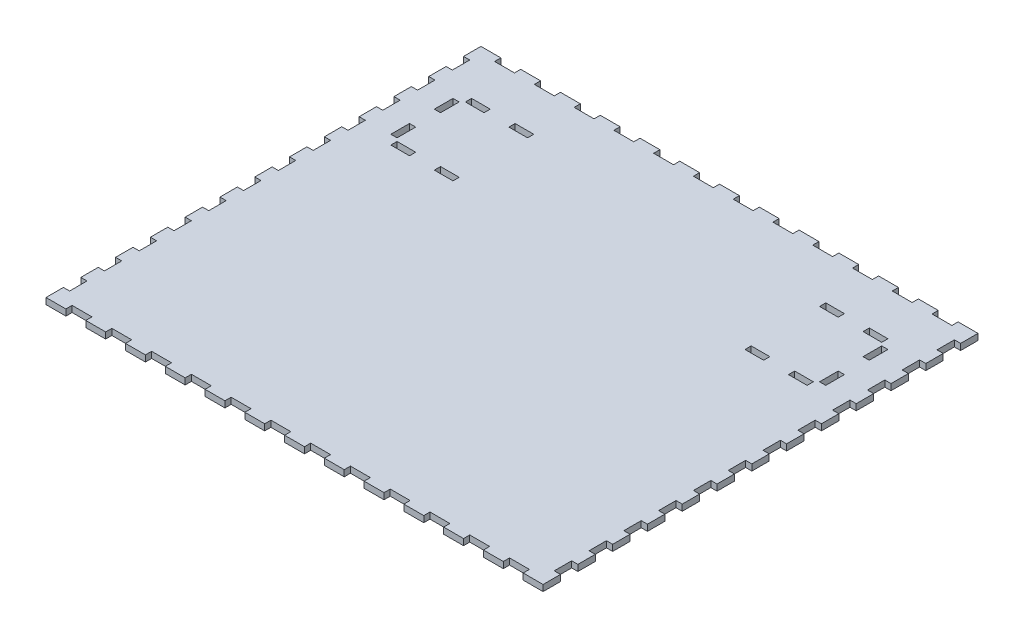
SolidWorks part; units mm, degrees
ref_plane "Plan de face" through (0, 0, 0) normal (0, 0, 1) x (1, 0, 0)
ref_plane "Plan de dessus" through (0, 0, 0) normal (0, 1, 0) x (1, 0, 0)
ref_plane "Plan de droite" through (0, 0, 0) normal (1, 0, 0) x (0, 0, -1)
sketch "Esquisse1" plane through (0, 0, 0) normal (0, 1, 0) x (1, 0, 0)
  line L1 (0, 0) -> (400, 0)
  line L2 (0, 0) -> (0, -350)
  line L3 (0, -350) -> (400, -350)
  line L4 (400, 0) -> (400, -350)
  dimension "D1" = 400
  dimension "D2" = 350
extrude "Boss.-Extru.1" add sketch "Esquisse1" along normal blind 5
ref_plane "Plan2" through (0, 0, 175) normal (0, 0, -1) x (-1, 0, 0)
ref_plane "Plan3" through (200, 0, 0) normal (1, 0, 0) x (0, 0, -1)
sketch "Esquisse2" plane through (0, 5, 0) normal (0, 1, 0) x (1, 0, 0)
  line L0 (400, 0) -> (0, 0) construction
  line L1 (16, 0) -> (32, 0)
  line L2 (16, 0) -> (16, -5)
  line L3 (16, -5) -> (32, -5)
  line L4 (32, 0) -> (32, -5)
  line L7 (0, 0) -> (400, 0) construction
  line L8 (0, 0) -> (0, -350) construction
  dimension "D1" = 400
  dimension "D2" = 16
  dimension "D3" = 16
  dimension "D4" = 5
extrude "Enlèv. mat.-Extru.1" cut sketch "Esquisse2" against normal blind 5
pattern_linear "Répétition linéaire1" count 12 spacing 32 along (1, 0, 0) of "Enlèv. mat.-Extru.1"
sketch "Esquisse3" plane through (0, 5, 0) normal (0, 1, 0) x (1, 0, 0)
  line L0 (0, 0) -> (0, -350) construction
  line L1 (0, -14) -> (5, -14)
  line L2 (0, -14) -> (0, -28)
  line L3 (0, -28) -> (5, -28)
  line L4 (5, -14) -> (5, -28)
  line L5 (0, 0) -> (0, -350) construction
  line L6 (0, -350) -> (400, -350) construction
  line L7 (16, 0) -> (0, 0) construction
  point P11 (-75.5806, -350)
  point P12 (0, -350)
  point P13 (0, -350)
  point P15 (0, 0)
  point P16 (0, 0)
  point P17 (0, -350)
  point P18 (0, -350)
  point P19 (0, -350)
  point P20 (0, -350)
  dimension "D4" = 5
  dimension "D1" = 350
  dimension "D2" = 14
  dimension "D3" = 14
extrude "Enlèv. mat.-Extru.2" cut sketch "Esquisse3" against normal blind 5
pattern_linear "Répétition linéaire2" count 12 spacing 28 along (0, 0, 1) of "Enlèv. mat.-Extru.2"
mirror "Symétrie1" about plane through (0, 0, 175) normal (0, 0, -1) of "Répétition linéaire1"
mirror "Symétrie2" about plane through (200, 0, 0) normal (1, 0, 0) of "Répétition linéaire2"
sketch "Esquisse4" plane through (0, 5, 0) normal (0, 1, 0) x (1, 0, 0)
  line L0 (48, 0) -> (32, 0) construction
  line L1 (32.5, -40) -> (47.5, -40)
  line L2 (32.5, -40) -> (32.5, -45)
  line L3 (32.5, -45) -> (47.5, -45)
  line L4 (47.5, -40) -> (47.5, -45)
  line L5 (67.5, -40) -> (82.5, -40)
  line L6 (67.5, -40) -> (67.5, -45)
  line L7 (67.5, -45) -> (82.5, -45)
  line L8 (82.5, -40) -> (82.5, -45)
  line L9 (32.5, -100) -> (47.5, -100)
  line L10 (32.5, -100) -> (32.5, -105)
  line L11 (32.5, -105) -> (47.5, -105)
  line L12 (47.5, -100) -> (47.5, -105)
  line L13 (67.5, -100) -> (82.5, -100)
  line L14 (67.5, -100) -> (67.5, -105)
  line L15 (67.5, -105) -> (82.5, -105)
  line L16 (82.5, -100) -> (82.5, -105)
  line L17 (47.5, -45) -> (67.5, -100) construction
  line L18 (67.5, -45) -> (47.5, -100) construction
  line L19 (200, -2.75) -> (200, 2.75) construction
  line L20 (57.5, -72.5) -> (-23.7594, -72.5) construction
  line L21 (30, -47.5) -> (25, -47.5)
  line L22 (30, -47.5) -> (30, -62.5)
  line L23 (30, -62.5) -> (25, -62.5)
  line L24 (25, -47.5) -> (25, -62.5)
  line L25 (25, -82.5) -> (30, -82.5)
  line L26 (25, -82.5) -> (25, -97.5)
  line L27 (25, -97.5) -> (30, -97.5)
  line L28 (30, -82.5) -> (30, -97.5)
  point P18 (57.5, -72.5)
  dimension "D1" = 5
  dimension "D2" = 15
  dimension "D4" = 15
  dimension "D5" = 20
  dimension "D7" = 5
  dimension "D11" = 55
  dimension "D12" = 40
  dimension "D13" = 142.5
  dimension "D14" = 175
  dimension "D15" = 5
  dimension "D3" = 15
  dimension "D6" = 15
  dimension "D8" = 20
  dimension "D9" = 10
extrude "Enlèv. mat.-Extru.3" cut sketch "Esquisse4" against normal blind 5
mirror "Symétrie3" about plane through (200, 0, 0) normal (1, 0, 0) of "Enlèv. mat.-Extru.3"
equation "\"D2@Esquisse2\"=\"D1@Esquisse2\"/25"
equation "\"D3@Esquisse2\"=\"D2@Esquisse2\""
equation "\"D4@Répétition linéaire1\"=\"D2@Esquisse2\"*2"
equation "\"D3@Répétition linéaire1\"=\"D2@Esquisse2\"*2"
equation "\"D2@Esquisse3\"=\"D1@Esquisse3\"/25"
equation "\"D3@Esquisse3\"=\"D2@Esquisse3\""
equation "\"D3@Répétition linéaire2\"=\"D2@Esquisse3\"*2"
equation "\"D4@Esquisse4\"=\"D2@Esquisse4\""
equation "\"D7@Esquisse4\"=\"D1@Esquisse4\""
equation "\"D13@Esquisse4\"=285/2"
equation "\"D14@Esquisse4\"=350/2"
equation "\"D15@Esquisse4\"=\"D1@Esquisse4\""
equation "\"D3@Esquisse4\"=\"D2@Esquisse4\""
equation "\"D6@Esquisse4\"=\"D2@Esquisse4\""
equation "\"D8@Esquisse4\"=\"D5@Esquisse4\""
equation "\"D9@Esquisse4\"=\"D8@Esquisse4\"/2"
